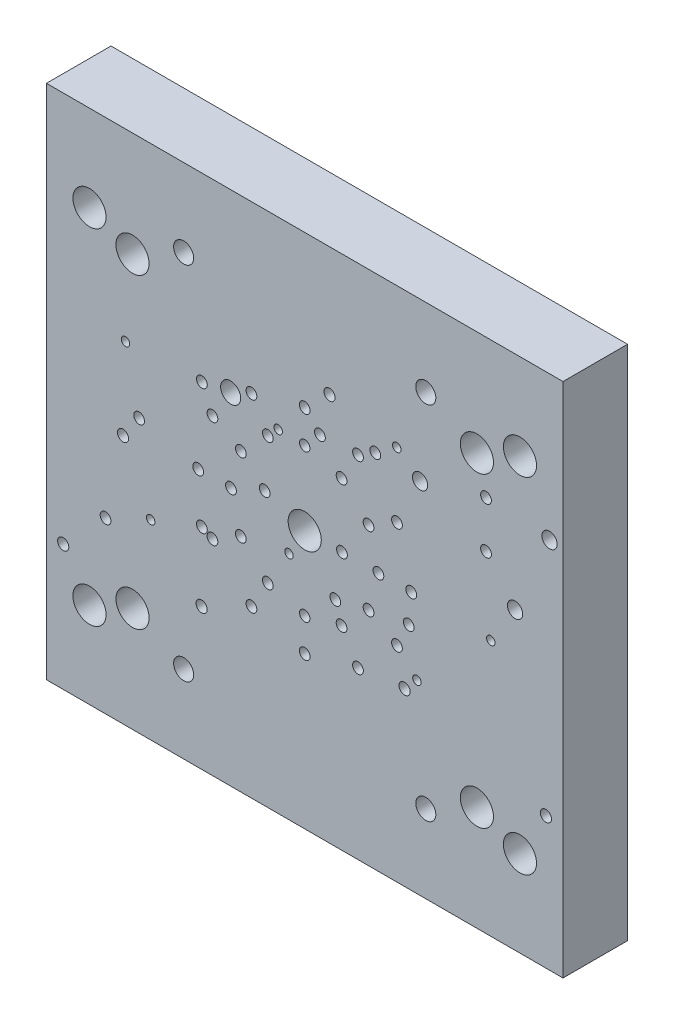
SolidWorks part; units mm, degrees
ref_plane "Front Plane" through (0, 0, 0) normal (0, 0, 1) x (1, 0, 0)
ref_plane "Top Plane" through (0, 0, 0) normal (0, 1, 0) x (1, 0, 0)
ref_plane "Right Plane" through (0, 0, 0) normal (1, 0, 0) x (0, 0, -1)
sketch "Sketch1" plane through (0, 0, 0) normal (0, 0, 1) x (1, 0, 0)
  line L1 (-152.4, 152.4) -> (152.4, 152.4)
  line L2 (-152.4, 152.4) -> (-152.4, -152.4)
  line L3 (-152.4, -152.4) -> (152.4, -152.4)
  line L4 (152.4, 152.4) -> (152.4, -152.4)
  line L5 (-152.4, 152.4) -> (152.4, -152.4) construction
  line L6 (-152.4, -152.4) -> (152.4, 152.4) construction
  point P0 (0, 0)
  dimension "D1" = 304.8
  dimension "D2" = 304.8
extrude "Boss-Extrude1" add sketch "Sketch1" along normal blind 38.1
sketch "Sketch2" plane through (0, 0, 38.1) normal (0, 0, 1) x (1, 0, 0)
  line L0 (-152.4, 0) -> (152.4, 0) construction
  line L5 (-152.4, 152.4) -> (-152.4, -152.4) construction
  line L6 (152.4, -152.4) -> (152.4, 152.4) construction
  line L7 (-152.4, -101.6) -> (152.4, -101.6) construction
  line L8 (-152.4, 101.6) -> (152.4, 101.6) construction
  line L9 (0, 101.6) -> (0, -101.6) construction
  line L10 (127, 101.6) -> (127, -101.6) construction
  line L11 (-127, 101.6) -> (-127, -101.6) construction
  circle A0 centre (-127, 101.6) radius 6.5151
  circle A1 centre (127, 101.6) radius 6.5151
  circle A2 centre (127, -101.6) radius 6.5151
  circle A3 centre (-127, -101.6) radius 6.5151
  circle A4 centre (0, 0) radius 6.5151
  dimension "D5" = 13.0302
  dimension "D1" = 101.6
  dimension "D2" = 101.6
  dimension "D3" = 127
  dimension "D4" = 127
extrude "HAAS T-Slot Holes" cut sketch "Sketch2" against normal through all
sketch "Sketch3" plane through (0, 0, 38.1) normal (0, 0, 1) x (1, 0, 0)
  circle A0 centre (-127, 101.6) radius 9.779
  circle A1 centre (127, 101.6) radius 9.779
  circle A2 centre (0, 0) radius 9.779
  circle A3 centre (127, -101.6) radius 9.779
  circle A4 centre (-127, -101.6) radius 9.779
  dimension "D1" = 19.558
extrude "HAAS Counter Bores" cut sketch "Sketch3" against normal offset from surface (22.225 mm away) 15.875 contours A0 | A1 | A2 | A3 | A4 up to face at (6.5151, 0, 0)
sketch "Sketch4" plane through (0, 0, 38.1) normal (0, 0, 1) x (1, 0, 0)
  line L0 (-127, 90.4875) -> (127, 90.4875) construction
  line L1 (-127, 30.1625) -> (127, 30.1625) construction
  line L2 (-127, 30.1625) -> (-127, -30.1625) construction
  line L3 (-127, -30.1625) -> (127, -30.1625) construction
  line L4 (127, 30.1625) -> (127, -30.1625) construction
  line L5 (-127, 30.1625) -> (127, -30.1625) construction
  line L6 (-127, -30.1625) -> (127, 30.1625) construction
  line L7 (-127, -90.4875) -> (127, -90.4875) construction
  line L8 (-101.6, 90.4875) -> (-101.6, 84.1375) construction
  line L9 (-101.6, -90.4875) -> (-101.6, -84.1375) construction
  line L10 (101.6, -90.4875) -> (101.6, -84.1375) construction
  line L11 (101.6, 90.4875) -> (101.6, 84.1375) construction
  circle A0 centre (-101.6, 90.4875) radius 6.5151
  circle A1 centre (101.6, 90.4875) radius 6.5151
  circle A2 centre (-101.6, -90.4875) radius 6.5151
  circle A3 centre (101.6, -90.4875) radius 6.5151
  point P0 (0, 0)
  dimension "D9" = 13.0302
  dimension "D1" = 60.325
  dimension "D2" = 254
  dimension "D5" = 203.2
  dimension "D6" = 25.4
  dimension "D7" = 203.2
  dimension "D8" = 6.35
  dimension "D3" = 60.325
  dimension "D4" = 60.325
extrude "Tormach T-Slot Holes" cut sketch "Sketch4" against normal through all
sketch "Sketch5" plane through (0, 0, 38.1) normal (0, 0, 1) x (1, 0, 0)
  circle A0 centre (-101.6, 90.4875) radius 9.779
  circle A1 centre (101.6, 90.4875) radius 9.779
  circle A2 centre (101.6, -90.4875) radius 9.779
  circle A3 centre (-101.6, -90.4875) radius 9.779
  dimension "D1" = 19.558
extrude "Tormach Counter bores" cut sketch "Sketch5" against normal up to surface (22.225 mm away) up to face at (-117.221, 101.6, 15.875)
sketch "Sketch6" plane through (0, 0, 38.1) normal (0, 0, 1) x (1, 0, 0)
  circle A0 centre (0, 0) radius 43.5 construction
  circle A1 centre (0, 43.5) radius 3.0734
  circle A2 centre (0, -43.5) radius 3.0734
  dimension "D1" = 87.0001
  dimension "D2" = 6.1468
extrude "Sprocket Locating Holes" cut sketch "Sketch6" against normal blind 6.35
sketch "Sketch7" plane through (0, 0, 38.1) normal (0, 0, 1) x (1, 0, 0)
  circle A0 centre (0, 0) radius 43.5 construction
  circle A2 centre (43.5, 0) radius 3.175
  circle A4 centre (37.6721, -21.75) radius 3.175
  circle A5 centre (21.75, -37.6721) radius 3.175
  circle A6 centre (0, -43.5) radius 3.175 [skipped]
  circle A7 centre (-21.75, -37.6721) radius 3.175
  circle A8 centre (-37.6721, -21.75) radius 3.175
  circle A9 centre (-43.5, 0) radius 3.175
  circle A10 centre (-37.6721, 21.75) radius 3.175
  circle A11 centre (-21.75, 37.6721) radius 3.175
  circle A12 centre (0, 43.5) radius 3.175 [skipped]
  circle A13 centre (21.75, 37.6721) radius 3.175
  circle A14 centre (37.6721, 21.75) radius 3.175
  point P31 (0, 0)
  dimension "D1" = 87.0001
  dimension "D2" = 6.35
  dimension "D3" = 12
extrude "Sprocket Mounting clearance holes" cut sketch "Sketch7" against normal blind 9.525
sketch "Sketch8" plane through (0, 0, 38.1) normal (0, 0, 1) x (1, 0, 0)
  line L1 (-71.4375, 106.4641) -> (71.4375, 106.4641) construction
  line L2 (-71.4375, 106.4641) -> (-71.4375, -106.4641) construction
  line L3 (-71.4375, -106.4641) -> (71.4375, -106.4641) construction
  line L4 (71.4375, 106.4641) -> (71.4375, -106.4641) construction
  line L5 (-71.4375, 106.4641) -> (71.4375, -106.4641) construction
  line L6 (-71.4375, -106.4641) -> (71.4375, 106.4641) construction
  circle A0 centre (-71.4375, 106.4641) radius 5.9182
  circle A1 centre (71.4375, 106.4641) radius 5.9182
  circle A2 centre (71.4375, -106.4641) radius 5.9182
  circle A3 centre (-71.4375, -106.4641) radius 5.9182
  point P0 (0, 0)
  dimension "D3" = 11.8364
  dimension "D1" = 142.875
  dimension "D2" = 212.9282
extrude "1/2-13 Tapped Holes" cut sketch "Sketch8" against normal blind 19.05
sketch "Sketch9" plane through (0, 0, 38.1) normal (0, 0, 1) x (1, 0, 0)
  circle A0 centre (-117.5189, -52.2876) radius 3.175
  circle A1 centre (-60.6634, -28.4101) radius 3.175
  circle A2 centre (-60.6634, 45.677) radius 3.175
  circle A3 centre (-23.6198, 8.6335) radius 3.175
  circle A4 centre (-97.707, 8.6335) radius 3.175
  circle A5 centre (18.0623, -26.1797) radius 3.175
  circle A6 centre (21.9762, 0) radius 3.175
  circle A7 centre (61.3833, -17.3739) radius 3.175
  circle A8 centre (106.976, 70.3959) radius 3.175
  circle A9 centre (106.976, 42.9004) radius 3.175
  circle A10 centre (144.4539, 67.4373) radius 4.5
  circle A11 centre (124.1092, 21.6131) radius 4.5
  circle A12 centre (68.0681, 59.3279) radius 4.5
  circle A13 centre (58.9353, -51.2652) radius 3.3
  circle A14 centre (-142.4923, -78.095) radius 3.3
  circle A15 centre (-105.7351, 43.7713) radius 2.5
  circle A16 centre (-90.8975, -39.8642) radius 2.5
  circle A17 centre (-9.2711, -16.3656) radius 2.5
  circle A18 centre (-15.6655, 43.8657) radius 2.5
  circle A20 centre (14.6267, 76.8405) radius 3.3
  circle A21 centre (8.9855, 53.4682) radius 3.175
  circle A22 centre (41.6559, 60.6579) radius 3.175
extrude "SSB Holes" cut sketch "Sketch9" against normal blind 19.05
ref_axis "Axis1" through (0, 0, 0) along (0, 0, 1)
sketch "Sketch10" plane through (0, 0, 38.1) normal (0, 0, 1) x (1, 0, 0)
  circle A0 centre (0, 0) radius 62.865 construction
  circle A1 centre (0, 62.865) radius 3.175
  circle A13 centre (31.4325, 54.4427) radius 3.175
  circle A14 centre (54.4427, 31.4325) radius 3.175
  circle A15 centre (62.865, 0) radius 3.175
  circle A16 centre (54.4427, -31.4325) radius 3.175
  circle A17 centre (31.4325, -54.4427) radius 3.175
  circle A18 centre (0, -62.865) radius 3.175
  circle A19 centre (-31.4325, -54.4427) radius 3.175
  circle A20 centre (-54.4427, -31.4325) radius 3.175
  circle A21 centre (-62.865, 0) radius 3.175
  circle A22 centre (-54.4427, 31.4325) radius 3.175
  circle A23 centre (-31.4325, 54.4427) radius 3.175
  point P30 (0, 0)
  point P56 (0, 0)
  dimension "D1" = 125.73
  dimension "D2" = 6.35
  dimension "D4" = 12
extrude "Sprocket Countersunk Holes" cut sketch "Sketch10" against normal blind 19.05
sketch "Sketch12" plane through (0, 0, 38.1) normal (0, 0, 1) x (1, 0, 0)
  circle A0 centre (-107.2144, -4.9977) radius 3.3
  circle A1 centre (-60.8212, -69.1392) radius 3.3
  circle A2 centre (142.3129, -74.567) radius 3.3
  circle A4 centre (54.3307, 69.7186) radius 2.4964
  circle A5 centre (109.7823, -1.2607) radius 2.5
  circle A6 centre (66.2094, -43.3332) radius 2.5
  circle A7 centre (-43.6886, 48.7489) radius 5.9182
  circle A8 centre (-71.4375, 106.4641) radius 5.9182 construction
extrude "DSB Holes" cut sketch "Sketch12" against normal blind 19.05
